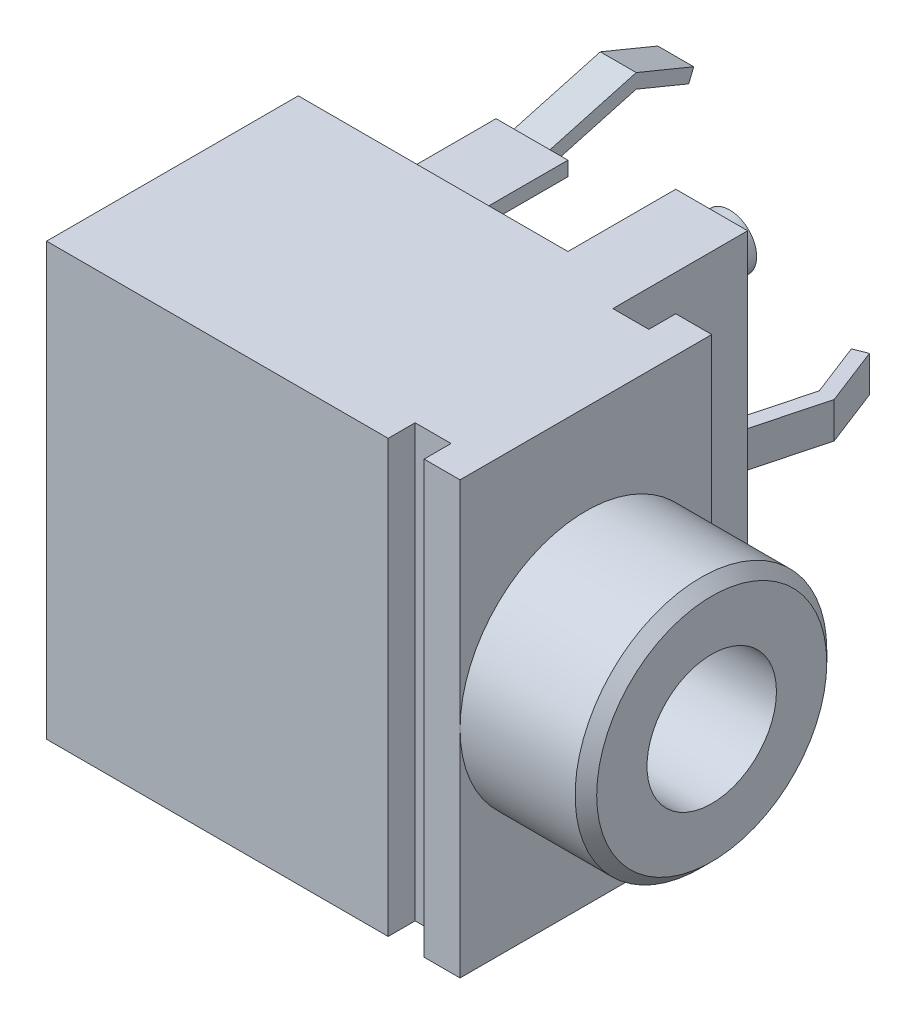
SolidWorks part; units mm, degrees
ref_plane "Plano frontal" through (0, 0, 0) normal (0, 0, 1) x (1, 0, 0)
ref_plane "Plano superior" through (0, 0, 0) normal (0, 1, 0) x (1, 0, 0)
ref_plane "Plano direito" through (0, 0, 0) normal (1, 0, 0) x (0, 0, -1)
ref_plane "Plano1" through (0, 0, -3.5) normal (0, 0, -1) x (-1, 0, 0)
sketch "Esboço1" plane through (0, 0, -3.5) normal (0, 0, -1) x (-1, 0, 0)
  line L0 (3.5, 6) -> (3.5, -6)
  line L1 (3.5, -6) -> (15, -6)
  line L2 (15, -6) -> (15, 6)
  line L3 (15, 6) -> (3.5, 6)
extrude "Ressalto-extrusão1" add sketch "Esboço1" against normal blind 7
sketch "Esboço2" plane through (0, 6, 0) normal (0, 1, 0) x (-1, 0, 0)
  line L0 (15, -2.75) -> (4.5, -2.75)
  line L1 (4.5, -2.75) -> (4.5, -3.5)
  line L2 (4.5, -3.5) -> (15, -3.5)
  line L3 (15, -3.5) -> (15, -2.75)
extrude "Corte-extrusão1" cut sketch "Esboço2" against normal through all
sketch "Esboço3" plane through (0, 0, -2.75) normal (0, 0, -1) x (-1, 0, 0)
  line L0 (15, -6) -> (5.5, -6)
  line L1 (5.5, -6) -> (5.5, 6)
  line L2 (5.5, 6) -> (15, 6)
  line L3 (15, 6) -> (15, -6)
extrude "Ressalto-extrusão2" add sketch "Esboço3" along normal blind 3.75
sketch "Esboço4" plane through (0, -6, 0) normal (0, -1, 0) x (1, 0, 0)
  line L0 (-7.5, -3.5) -> (-15, -3.5)
  line L1 (-15, -3.5) -> (-15, -6.5)
  line L2 (-15, -6.5) -> (-7.5, -6.5)
  line L3 (-7.5, -6.5) -> (-7.5, -3.5)
extrude "Corte-extrusão2" cut sketch "Esboço4" against normal through all
sketch "Esboço5" plane through (0, 0, -3.5) normal (0, 0, -1) x (-1, 0, 0)
  line L0 (12.5, -2.3) -> (12.5, -2.7)
  line L1 (12.5, -2.7) -> (10.5, -2.7)
  line L2 (10.5, -2.7) -> (10.5, -2.3)
  line L3 (10.5, -2.3) -> (12.5, -2.3)
extrude "Ressalto-extrusão3" add sketch "Esboço5" along normal blind 7
sketch "Esboço6" plane through (0, -2.7, 0) normal (0, -1, 0) x (1, 0, 0)
  line L0 (-10.5, -6.5) -> (-11, -6.5)
  line L1 (-11, -6.5) -> (-11, -10.5)
  line L2 (-11, -10.5) -> (-10.5, -10.5)
  line L3 (-10.5, -10.5) -> (-10.5, -6.5)
extrude "Corte-extrusão3" cut sketch "Esboço6" against normal through all
sketch "Esboço7" plane through (0, -2.7, 0) normal (0, -1, 0) x (1, 0, 0)
  line L0 (-12, -6.5) -> (-12.5, -6.5)
  line L1 (-12.5, -6.5) -> (-12.5, -10.5)
  line L2 (-12.5, -10.5) -> (-12, -10.5)
  line L3 (-12, -10.5) -> (-12, -6.5)
extrude "Corte-extrusão4" cut sketch "Esboço7" against normal through all
sketch "Esboço8" plane through (0, 0, -3.5) normal (0, 0, -1) x (-1, 0, 0)
  line L0 (7.5, 1) -> (12.25, 1)
  line L1 (12.25, 1) -> (12.25, -1)
  line L2 (12.25, -1) -> (7.5, -1)
  line L3 (7.5, -1) -> (7.5, 1)
extrude "Ressalto-extrusão4" add sketch "Esboço8" along normal blind 3
sketch "Esboço9" plane through (0, -6, 0) normal (0, -1, 0) x (1, 0, 0)
  line L0 (-5.5, 3.5) -> (-5.5, 2.75)
  line L1 (-5.5, 2.75) -> (-4.5, 2.75)
  line L2 (-4.5, 2.75) -> (-4.5, 3.5)
  line L3 (-4.5, 3.5) -> (-5.5, 3.5)
extrude "Corte-extrusão5" cut sketch "Esboço9" against normal through all
sketch "Esboço10" plane through (0, 0, -3.5) normal (0, 0, -1) x (-1, 0, 0)
  line L0 (10.5, 4.8) -> (10.5, 5.2)
  line L1 (10.5, 5.2) -> (12.5, 5.2)
  line L2 (12.5, 5.2) -> (12.5, 4.8)
  line L3 (12.5, 4.8) -> (10.5, 4.8)
extrude "Ressalto-extrusão5" add sketch "Esboço10" along normal blind 3
sketch "Esboço11" plane through (0, 0, -3.5) normal (0, 0, -1) x (-1, 0, 0)
  line L0 (12.5, -4.8) -> (12.5, -5.2)
  line L1 (12.5, -5.2) -> (10.5, -5.2)
  line L2 (10.5, -5.2) -> (10.5, -4.8)
  line L3 (10.5, -4.8) -> (12.5, -4.8)
extrude "Ressalto-extrusão6" add sketch "Esboço11" along normal blind 3
sketch "Esboço12" plane through (0, 0, -3.5) normal (0, 0, -1) x (-1, 0, 0)
  line L0 (12.5, 2.7) -> (12.5, 2.3)
  line L1 (12.5, 2.3) -> (10.5, 2.3)
  line L2 (10.5, 2.3) -> (10.5, 2.7)
  line L3 (10.5, 2.7) -> (12.5, 2.7)
extrude "Ressalto-extrusão7" add sketch "Esboço12" along normal blind 3
sketch "Esboço13" plane through (0, 0, -6.5) normal (0, 0, -1) x (-1, 0, 0)
  line L0 (12, 0.2) -> (12, -0.2)
  line L1 (12, -0.2) -> (11, -0.2)
  line L2 (11, -0.2) -> (11, 0.2)
  line L3 (11, 0.2) -> (12, 0.2)
extrude "Ressalto-extrusão8" add sketch "Esboço13" along normal blind 0.5
ref_plane "Plano2" through (0, -5, 0) normal (0, 1, 0) x (1, 0, 0)
sketch "Esboço14" plane through (0, -5, 0) normal (0, 1, 0) x (1, 0, 0)
  line L0 (-5.75, 7) -> (-6.5, 7)
  line L1 (-6.5, 7) -> (-6.5, 6.5)
  line L2 (-6.5, 6.5) -> (-5.75, 6.5)
  line L3 (-5.75, 6.5) -> (-5.75, 7)
  line L4 (-6.5, 7) -> (-6.5, 6.5) construction
revolve "Revolução1" add sketch "Esboço14" angle 360 about L4 reverse direction yes
ref_plane "Plano3" through (0, 5, 0) normal (0, 1, 0) x (1, 0, 0)
sketch "Esboço15" plane through (0, 5, 0) normal (0, 1, 0) x (1, 0, 0)
  line L0 (-5.75, 7) -> (-6.5, 7)
  line L1 (-6.5, 7) -> (-6.5, 6.5)
  line L2 (-6.5, 6.5) -> (-5.75, 6.5)
  line L3 (-5.75, 6.5) -> (-5.75, 7)
  line L4 (-6.5, 7) -> (-6.5, 6.5) construction
revolve "Revolução2" add sketch "Esboço15" angle 360 about L4 reverse direction yes
ref_plane "Plano4" through (0, 0, 0) normal (0, 0, -1) x (-1, 0, 0)
sketch "Esboço16" plane through (0, 0, 0) normal (0, 0, -1) x (-1, 0, 0)
  line L0 (0, 3.5) -> (0, 0)
  line L1 (0, 0) -> (3.5, 0)
  line L2 (3.5, 0) -> (3.5, 3.5)
  line L3 (3.5, 3.5) -> (0, 3.5)
  line L4 (0, 0) -> (3.5, 0) construction
revolve "Revolução3" add sketch "Esboço16" angle 360 about L4 reverse direction yes
hole_wizard "Furo de diâmetro Ø3.6 (3.6)1" positions "Esboço18" profile "Esboço17" hole size "Ø3.6" standard "Ansi Metric"
sketch "Esboço18" plane through (0, 0, 0) normal (1, 0, 0) x (0, 0, -1)
  point P0 (0, 0)
sketch "Esboço17" plane through (0, 0, 0) normal (0, 1, 0) x (0, 0, -1)
  line L0 (0, 0) -> (0, 3.5)
  line L1 (0, 3.5) -> (1.8, 3.5)
  line L2 (1.8, 3.5) -> (1.8, 0)
  line L5 (1.8, 0) -> (0, 0)
  line L10 (0, 3.5) -> (-1.8, 3.5) construction
  line L11 (0, -6.35) -> (0, 107.95) construction
  dimension "Hole Dia." = 3.6
  dimension "Hole Depth" = 3.5
  dimension "Drill Angle" = 180
chamfer "Chanfro1" distance 0.3 angle 45 1 edges at (0, 0, 3.5)
sketch "Esboço19" plane through (0, 0, -6.5) normal (0, 0, -1) x (-1, 0, 0)
  line L0 (5.5, 6) -> (5.5, -6) construction
  line L1 (6.29, -0.5) -> (6.72, -0.5)
  line L2 (6.29, -0.5) -> (6.29, 0.5)
  line L3 (6.29, 0.5) -> (6.72, 0.5)
  line L4 (6.72, -0.5) -> (6.72, 0.5)
  dimension "D1" = 1
  dimension "D2" = 0.43
  dimension "D3" = 0.79
  dimension "D4" = 0.5
extrude "Ressalto-extrusão9" add sketch "Esboço19" along normal blind 0.5
sketch "Esboço20" plane through (0, 0, 0) normal (0, 1, 0) x (1, 0, 0)
  line L0 (-6.3022, 6.9875) -> (-5.7322, 9.1375)
  line L1 (-5.7322, 9.1375) -> (-6.3522, 10.7375)
  line L2 (-6.3022, 6.9875) -> (-6.7177, 6.9875)
  line L3 (-6.3522, 10.7375) -> (-6.7134, 10.5975)
  line L4 (-6.7177, 6.9875) -> (-6.1477, 9.1375)
  line L5 (-6.1477, 9.1375) -> (-6.7134, 10.5975)
  dimension "D1" = 2.15
  dimension "D2" = 0.57
  dimension "D3" = 1.6
  dimension "D4" = 0.62
extrude "Ressalto-extrusão10" add sketch "Esboço20" along normal mid plane 1
sketch "Esboço21" plane through (-12.5, 0, 0) normal (-1, 0, 0) x (0, 0, 1)
  line L0 (-6.5, 5.2) -> (-8.9, 5.86)
  line L1 (-8.9, 5.86) -> (-10.5, 5.2)
  line L2 (-6.5, 5.2) -> (-6.5, 4.8)
  line L3 (-6.5, 4.8) -> (-8.9, 5.46)
  line L4 (-8.9, 5.46) -> (-10.359, 4.8582)
  line L5 (-10.359, 4.8582) -> (-10.5, 5.2)
  dimension "D1" = 2.4
  dimension "D2" = 1.6
  dimension "D3" = 0.66
  dimension "D4" = 0.66
extrude "Ressalto-extrusão11" add sketch "Esboço21" against normal blind 1 from offset 0.5 offset against normal yes
mirror "Espelhar1" about plane through (0, 0, 0) normal (0, 1, 0) of "Ressalto-extrusão11"
